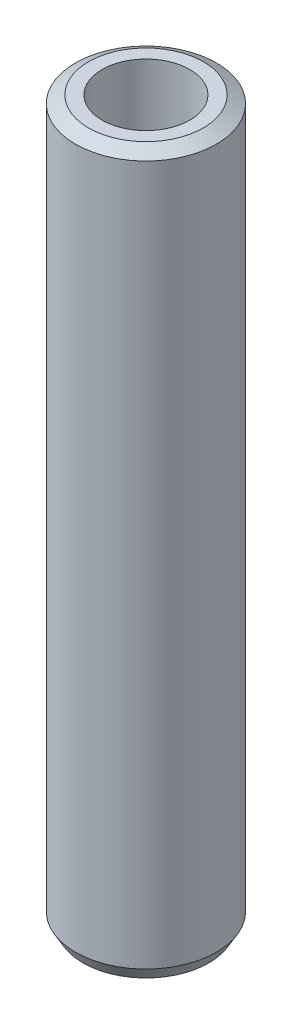
SolidWorks part; units mm, degrees
ref_plane "Front Plane" through (0, 0, 0) normal (0, 0, 1) x (1, 0, 0)
ref_plane "Top Plane" through (0, 0, 0) normal (0, 1, 0) x (1, 0, 0)
ref_plane "Right Plane" through (0, 0, 0) normal (1, 0, 0) x (0, 0, -1)
sketch "Sketch1" plane through (0, 0, 0) normal (0, 1, 0) x (1, 0, 0)
  circle A0 centre (0, 0) radius 40
  dimension "SHAFT_OD" = 80
extrude "Boss-Extrude1" add sketch "Sketch1" along normal blind 408.8549
sketch "Sketch2" plane through (0, 0, 0) normal (0, 1, 0) x (1, 0, 0)
  circle A0 centre (0, 0) radius 24.9022
  dimension "BORE_D" = 49.8045
extrude "Cut-Extrude1" cut sketch "Sketch2" along normal through all
chamfer "Chamfer1" distance 4.2875 angle 60 2 edges at (0, 408.8549, 40) (0, 0, 40) first distance on face at (0, 408.8549, 40) first distance on face at (0, 0, 24.9022)
